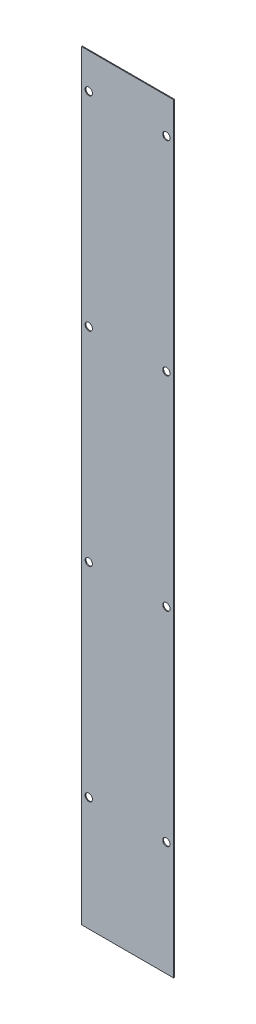
SolidWorks part; units mm, degrees
ref_plane "Front Plane" through (0, 0, 0) normal (0, 0, 1) x (1, 0, 0)
ref_plane "Top Plane" through (0, 0, 0) normal (0, 1, 0) x (1, 0, 0)
ref_plane "Right Plane" through (0, 0, 0) normal (1, 0, 0) x (0, 0, -1)
sketch "Sketch1" plane through (0, 0, 0) normal (0, 0, 1) x (1, 0, 0)
  line L1 (0, 0) -> (76, 0)
  line L2 (0, 0) -> (0, 627)
  line L3 (0, 627) -> (76, 627)
  line L4 (76, 0) -> (76, 627)
  dimension "D1" = 627
  dimension "D2" = 76
base flange "Base-Flange1" sketch "Sketch1" thickness 0.7 reverse thickness direction no parameters "D1"=1
sketch "Sketch2" plane through (0, 0, 0) normal (0, 0, 1) x (1, 0, 0)
  line L1 (76, 627) -> (0, 627) construction
  line L2 (38, 627) -> (38, 748.5) construction
  line L4 (76, 0) -> (76, 627) construction
  circle A12 centre (70, 598) radius 3
  circle A13 centre (70, 430) radius 3
  circle A14 centre (70, 262) radius 3
  circle A15 centre (70, 94) radius 3
  circle A16 centre (70, -74) radius 3
  circle A17 centre (6, -74) radius 3
  circle A18 centre (6, 94) radius 3
  circle A19 centre (6, 262) radius 3
  circle A20 centre (6, 430) radius 3
  circle A21 centre (6, 598) radius 3
  dimension "D1" = 6
  dimension "D2" = 6
  dimension "D3" = 29
  dimension "D4" = 5
extrude "Cut-Extrude1" cut sketch "Sketch2" against normal blind 10 normal cut yes
sketch "Bend-Lines1" [suppressed] plane through (0, 0, 0) normal (0, 1, 0) x (1, 0, 0)
sketch "Bounding-Box1" [suppressed] plane through (0, 0, 0) normal (0, 1, 0) x (1, 0, 0)
sheet metal parameters "Sheet-Metal1" thickness 0.7 parameters "D1"=1
flat pattern "Flat-Pattern1" [suppressed]
sketch "Bend-Lines2" plane through (0, 0, 0) normal (0, 1, 0) x (1, 0, 0)
sketch3d "Bounding-Box2" [suppressed]
  line L0 (240, 707, 0) -> (240, 0, 0) construction
  line L1 (0, 707, 0) -> (0, 0, 0) construction
  line L2 (240, 707, 0) -> (0, 707, 0) construction
  line L3 (240, 0, 0) -> (0, 0, 0) construction
sheet metal parameters "Sheet-Metal2" thickness 0.7 parameters "D1"=1
flat pattern "Flat-Pattern1"
sketch "Bend-Lines2" plane through (0, 0, 0) normal (0, 1, 0) x (1, 0, 0)
sketch3d "Bounding-Box2" [suppressed]
  line L0 (85, 806.5, 0) -> (85, 0, 0) construction
  line L1 (0, 806.5, 0) -> (0, 0, 0) construction
  line L2 (85, 806.5, 0) -> (0, 806.5, 0) construction
  line L3 (85, 0, 0) -> (0, 0, 0) construction
